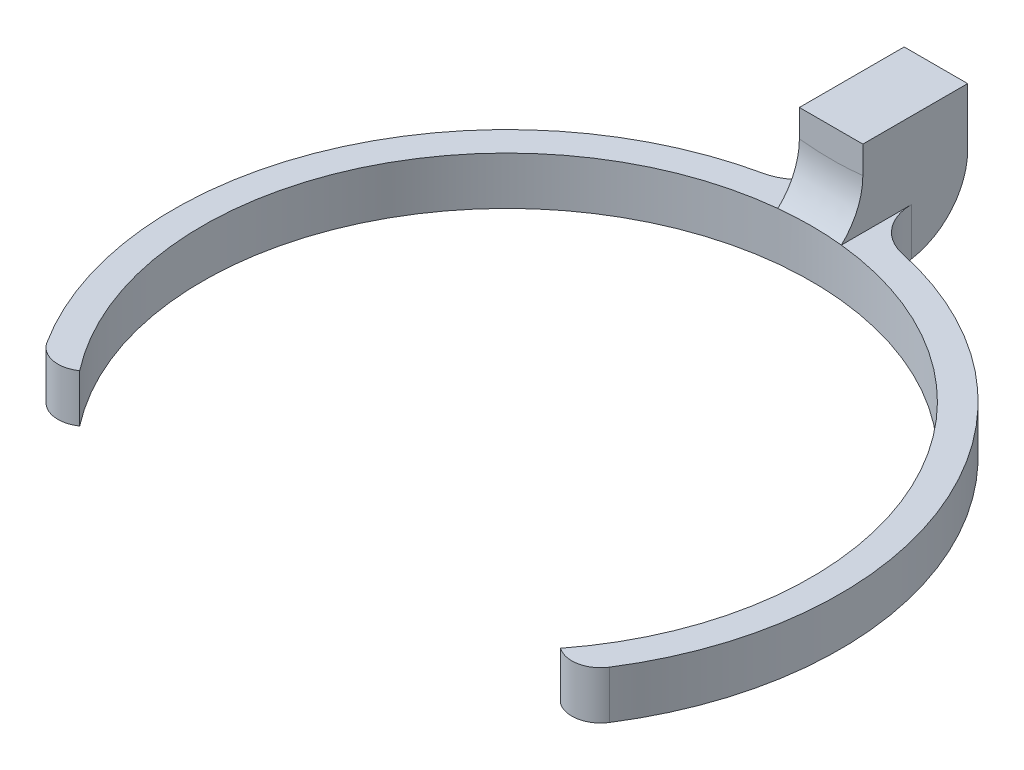
SolidWorks part; units mm, degrees
ref_plane "Front Plane" through (0, 0, 0) normal (0, 0, 1) x (1, 0, 0)
ref_plane "Top Plane" through (0, 0, 0) normal (0, 1, 0) x (1, 0, 0)
ref_plane "Right Plane" through (0, 0, 0) normal (1, 0, 0) x (0, 0, -1)
sketch "Sketch1" plane through (0, 0, 0) normal (0, 1, 0) x (1, 0, 0)
  line L0 (-2.369, -1.8407) -> (0, 0)
  line L1 (52.512, -1.8407) -> (50.1431, 0)
  line L3 (21.7544, 64.2303) -> (28.3743, 64.2303)
  line L4 (21.7544, 64.2303) -> (21.7544, 54.0716)
  line L5 (28.3743, 64.2303) -> (28.3743, 54.073)
  arc A0 (0, 0) -> (50.1431, 0) centre (25.0715, 19.4803) cw
  arc A1 (21.7544, 54.0716) -> (-2.369, -1.8407) centre (25.0715, 19.4803) ccw
  arc A2 (52.512, -1.8407) -> (28.3743, 54.073) centre (25.0715, 19.4803) ccw
  dimension "D1" = 31.75
  dimension "D3" = 34.75
extrude "Boss-Extrude1" add sketch "Sketch1" along normal blind 5
fillet "Fillet1" radius 5 2 edges at (21.7544, 2.5, -54.0716) (28.3743, 2.5, -54.073)
sketch "Sketch3" plane through (0, 5, 0) normal (0, 1, 0) x (1, 0, 0)
  line L0 (21.7544, 64.2303) -> (28.3743, 64.2303)
  line L1 (21.7544, 64.2303) -> (21.7544, 53.2998)
  line L2 (28.3743, 64.2303) -> (28.3743, 53.2998)
  line L3 (21.7544, 53.2998) -> (28.3743, 53.2998)
extrude "Boss-Extrude2" add sketch "Sketch3" along normal blind 8
fillet "Fillet4" radius 3 2 edges at (52.512, 2.5, 1.8407) (-2.369, 2.5, 1.8407)
fillet "Fillet6" radius 7 1 edges at (25.0643, 0, -64.2303)
fillet "Fillet7" radius 7 1 edges at (25.0643, 5, -53.2998)
